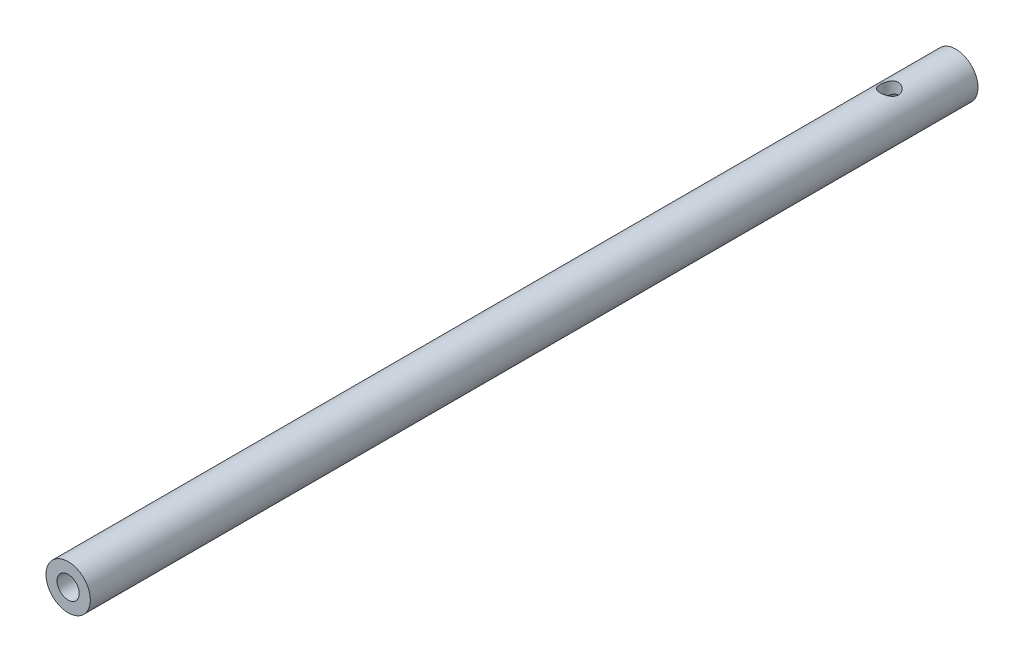
SolidWorks part; units mm, degrees
ref_plane "Front Plane" through (0, 0, 0) normal (0, 0, 1) x (1, 0, 0)
ref_plane "Top Plane" through (0, 0, 0) normal (0, 1, 0) x (1, 0, 0)
ref_plane "Right Plane" through (0, 0, 0) normal (1, 0, 0) x (0, 0, -1)
sketch "Sketch1" plane through (0, 0, 0) normal (0, 0, 1) x (1, 0, 0)
  circle A0 centre (0, 0) radius 6.35
  circle A1 centre (0, 0) radius 3.175
  dimension "D1" = 12.7
  dimension "D2" = 6.35
extrude "Boss-Extrude1" add sketch "Sketch1" along normal blind 254
sketch "Sketch2" plane through (0, 0, 0) normal (0, 1, 0) x (1, 0, 0)
  line L0 (6.35, 0) -> (-6.35, 0) construction
  circle A0 centre (0, -19.05) radius 2.6035
  dimension "D1" = 5.207
  dimension "D2" = 19.05
extrude "Cut-Extrude1" cut sketch "Sketch2" against normal blind 254 and the other way blind 254
